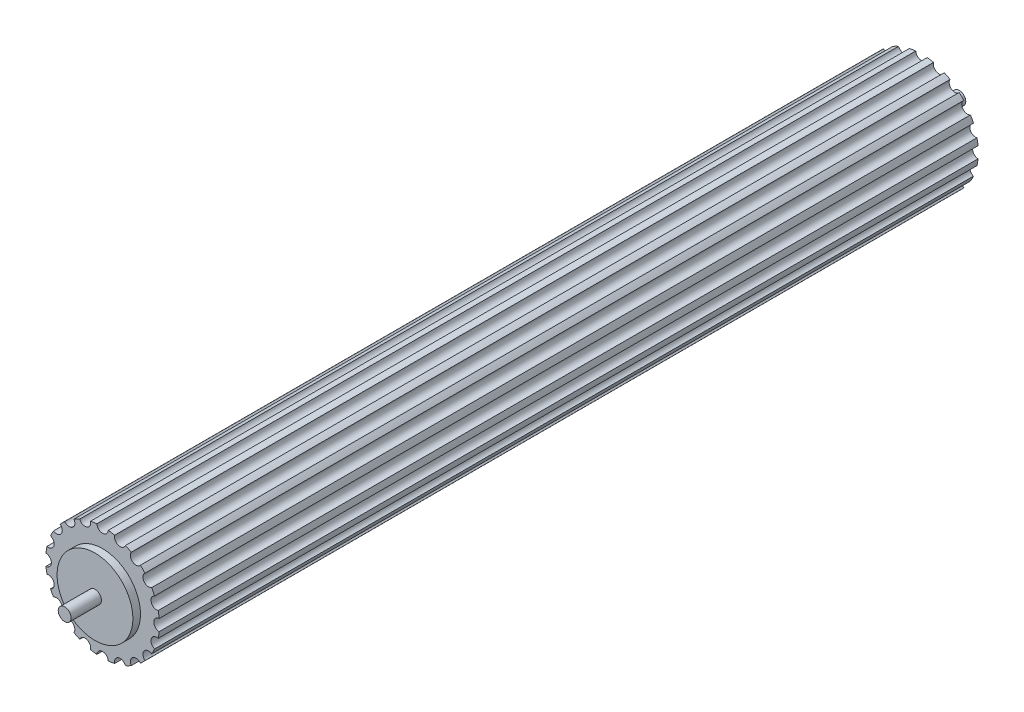
SolidWorks part; units mm, degrees
material "1060 Alaşım"
ref_plane "Ön Düzlem" through (0, 0, 0) normal (0, 0, 1) x (1, 0, 0)
ref_plane "Üst Düzlem" through (0, 0, 0) normal (0, 1, 0) x (1, 0, 0)
ref_plane "Sağ Düzlem" through (0, 0, 0) normal (1, 0, 0) x (0, 0, -1)
sketch "Çizim1" plane through (0, 0, 0) normal (0, 0, 1) x (1, 0, 0)
  circle A0 centre (0, 0) radius 75
  dimension "D1" = 150
extrude "Yükseklik-Ekstrüzyon1" add sketch "Çizim1" along normal blind 1080
sketch "Çizim2" plane through (0, 0, 1080) normal (0, 0, 1) x (1, 0, 0)
  circle A0 centre (0, 0) radius 8.5
  dimension "D1" = 17
extrude "Yükseklik-Ekstrüzyon2" add sketch "Çizim2" along normal blind 50
ref_plane "Düzlem1" through (0, 0, 540) normal (0, 0, 1) x (1, 0, 0)
mirror "Aynalama1" about plane through (0, 0, 540) normal (0, 0, 1) of "Yükseklik-Ekstrüzyon2"
sketch "Çizim3" plane through (0, 0, 1080) normal (0, 0, 1) x (1, 0, 0)
  circle A0 centre (0, 0) radius 50
  dimension "D1" = 100
extrude "Yükseklik-Ekstrüzyon3" add sketch "Çizim3" along normal blind 10
mirror "Aynalama2" about plane through (0, 0, 540) normal (0, 0, 1) of "Yükseklik-Ekstrüzyon3"
sketch "Çizim4" plane through (0, 0, 1080) normal (0, 0, 1) x (1, 0, 0)
  circle A0 centre (0, 75) radius 7.5
  circle A1 centre (0, 0) radius 75 construction
  dimension "D1" = 15
extrude "Kes-Ekstrüzyon1" cut sketch "Çizim4" against normal through all
ref_axis "Eksen1" through (0, 0, 1080) along (0, 0, -1)
pattern_circular "Dairesel Kaplama1" count 20 over 360 about axis through (0, 0, 1080) along (0, 0, -1) of "Kes-Ekstrüzyon1"
